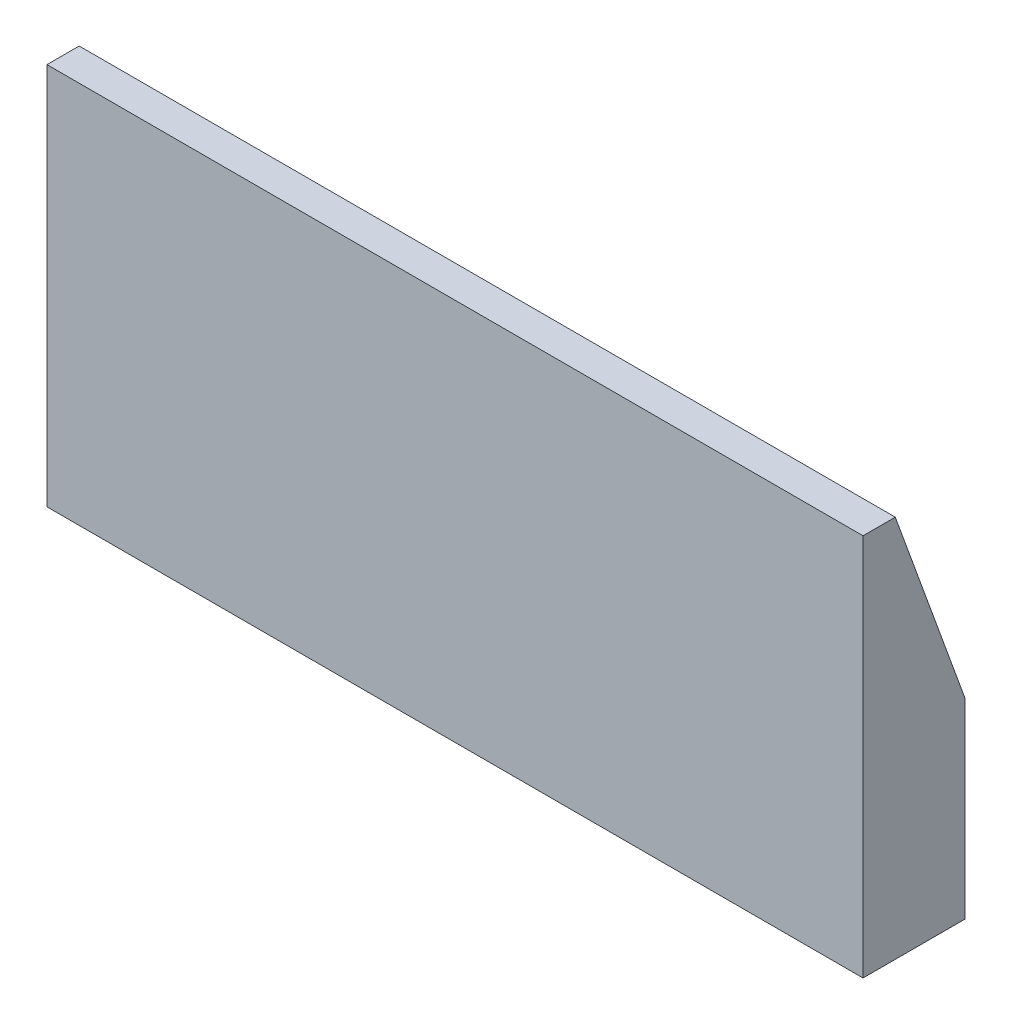
SolidWorks part; units mm, degrees
ref_plane "Front Plane" through (0, 0, 0) normal (0, 0, 1) x (1, 0, 0)
ref_plane "Top Plane" through (0, 0, 0) normal (0, 1, 0) x (1, 0, 0)
ref_plane "Right Plane" through (0, 0, 0) normal (1, 0, 0) x (0, 0, -1)
sketch "Sketch1" plane through (0, 0, 0) normal (1, 0, 0) x (0, 0, -1)
  line L0 (0, 0) -> (40, 0)
  line L1 (40, 0) -> (40, 75)
  line L2 (40, 75) -> (12.6384, 150.1754)
  line L3 (12.6384, 150.1754) -> (0, 150.1754)
  line L4 (0, 150.1754) -> (0, 0)
  dimension "D1" = 75
  dimension "D2" = 80
  dimension "D3" = 40
  dimension "D4" = 110
extrude "Boss-Extrude1" add sketch "Sketch1" along normal blind 320
equation "\"LED_matrix_height\"=75"
equation "\"D1@Sketch1\"=\"LED_matrix_height\""
equation "\"keypad_height\"=80"
equation "\"D2@Sketch1\"=\"keypad_height\""
equation "\"front_panel_width\"=40"
equation "\"D3@Sketch1\"=\"front_panel_width\""
equation "\"front_panel_length\"=320"
equation "\"D1@Boss-Extrude1\"=\"front_panel_length\""
equation "\"front_panel_incline\"=110"
equation "\"D4@Sketch1\"=\"front_panel_incline\""
